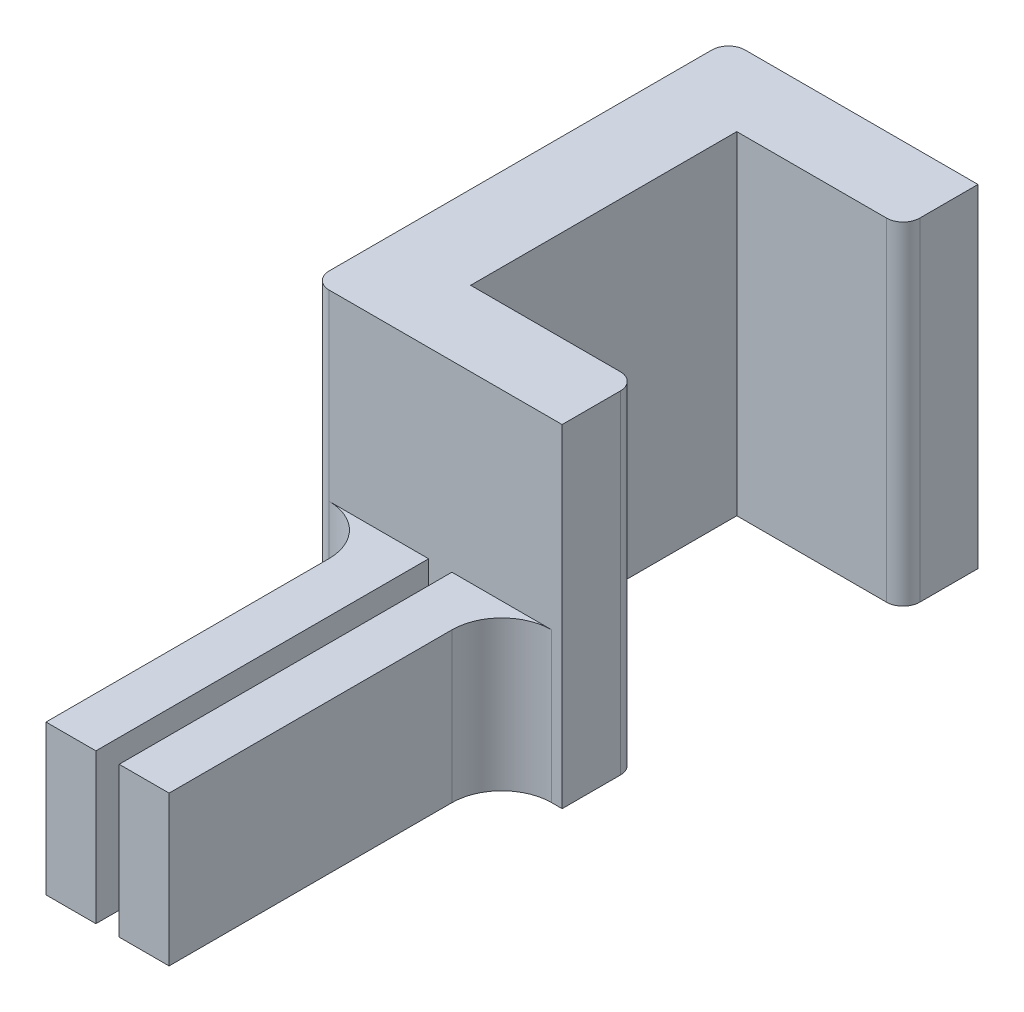
SolidWorks part; units mm, degrees
ref_plane "Front Plane" through (0, 0, 0) normal (0, 0, 1) x (1, 0, 0)
ref_plane "Top Plane" through (0, 0, 0) normal (0, 1, 0) x (1, 0, 0)
ref_plane "Right Plane" through (0, 0, 0) normal (1, 0, 0) x (0, 0, -1)
sketch "Sketch1" plane through (0, 0, 0) normal (0, 1, 0) x (1, 0, 0)
  line L0 (0, 0) -> (0, 25)
  line L1 (0, 25) -> (15, 25)
  line L2 (15, 25) -> (15, 20.5)
  line L3 (15, 20.5) -> (5, 20.5)
  line L4 (5, 20.5) -> (5, 4.5)
  line L5 (5, 4.5) -> (15, 4.5)
  line L6 (15, 4.5) -> (15, 0)
  line L7 (15, 0) -> (0, 0)
  point P9 (43.1186, 19.661)
  dimension "D1" = 16
  dimension "D2" = 25
  dimension "D3" = 5
  dimension "D4" = 10
extrude "Boss-Extrude1" add sketch "Sketch1" along normal blind 20
sketch "Sketch2" plane through (0, 0, 0) normal (0, 1, 0) x (1, 0, 0)
  line L0 (0, 0) -> (15, 0) construction
  line L1 (3.9739, 0) -> (6.9739, 0)
  line L2 (3.9739, 0) -> (3.9739, -20)
  line L3 (3.9739, -20) -> (6.9739, -20)
  line L4 (11.3739, 0) -> (11.3739, -20)
  line L5 (8.3739, -20) -> (11.3739, -20)
  line L7 (6.9739, -20) -> (6.9739, 0)
  line L9 (8.3739, -20) -> (8.3739, 0)
  line L10 (8.3739, 0) -> (11.3739, 0)
  dimension "D1" = 3
  dimension "D2" = 3
  dimension "D3" = 20
  dimension "D4" = 1.4
extrude "Boss-Extrude2" add sketch "Sketch2" along normal blind 9
fillet "Fillet1" radius 3 2 edges at (11.3739, 4.5, 0) (3.9739, 4.5, 0)
fillet "Fillet2" radius 1 2 edges at (15, 10, -20.5) (15, 10, -4.5)
fillet "Fillet3" radius 1 2 edges at (0, 10, -25) (0, 10, 0)
